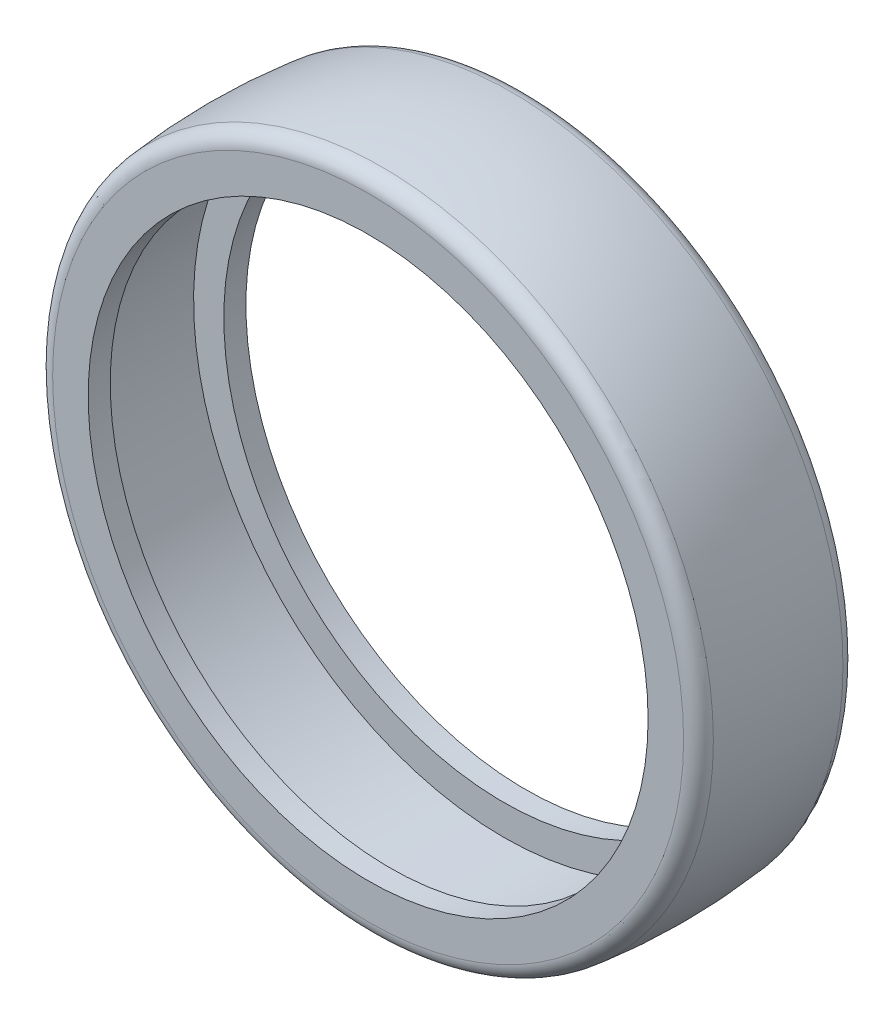
SolidWorks part; units mm, degrees
ref_plane "Front Plane" through (0, 0, 0) normal (0, 0, 1) x (1, 0, 0)
ref_plane "Top Plane" through (0, 0, 0) normal (0, 1, 0) x (1, 0, 0)
ref_plane "Right Plane" through (0, 0, 0) normal (1, 0, 0) x (0, 0, -1)
sketch "Sketch1" plane through (0, 0, 0) normal (1, 0, 0) x (0, 0, -1)
  line L0 (0, 0) -> (22.6821, 0) construction
  line L8 (-6, 26.625) -> (-3.9, 26.625)
  line L9 (-3.9, 26.625) -> (-3.9, 29.5)
  line L10 (-3.9, 29.5) -> (6.9, 29.5)
  line L11 (6.9, 29.5) -> (6.9, 26.625)
  line L12 (6.9, 26.625) -> (9, 26.625)
  line L13 (9, 26.625) -> (9, 31.83)
  line L14 (9, 31.83) -> (-6, 31.83)
  line L15 (-6, 31.83) -> (-6, 26.625)
  line L16 (-6, 26.625) -> (-3.9, 26.625)
  line L17 (-3.9, 26.625) -> (-3.9, 29.5)
  line L18 (-3.9, 29.5) -> (6.9, 29.5)
  line L19 (6.9, 29.5) -> (6.9, 26.625)
  line L20 (6.9, 26.625) -> (9, 26.625)
  line L21 (9, 26.625) -> (9, 31.83)
  line L22 (9, 31.83) -> (-6, 31.83)
  line L23 (-6, 31.83) -> (-6, 26.625)
  dimension "D1" = 0
revolve "Revolve1" add sketch "Sketch1" angle 360 about L0
sketch "Sketch2" plane through (0, 0, 0) normal (1, 0, 0) x (0, 0, -1)
  line L0 (-6, 31.83) -> (-6, -31.83) construction
  line L1 (9, -31.83) -> (9, 31.83) construction
  line L2 (9, -31.83) -> (9, 31.83) construction
  line L3 (9, 31.83) -> (-13.1922, 31.83) construction
  line L4 (-6, 31.33) -> (9, 31.33) construction
  line L5 (-6, 31.33) -> (-6, 34.2329)
  line L6 (-6, 34.2329) -> (9, 34.2329)
  line L7 (9, 34.2329) -> (9, 31.33)
  line L8 (0, 0) -> (21.0121, 0) construction
  arc A0 (-6, 31.33) -> (9, 31.33) centre (1.5, -24.67) cw
  dimension "D1" = 0.5
revolve "Cut-Revolve1" cut sketch "Sketch2" angle 360 about L8 region at (0, 32.9439, -1.5)
fillet "Fillet1" radius 1.5 2 edges at (31.33, 0, -9) (31.33, 0, 6)
sketch "Sketch3" plane through (0, 0, 0) normal (1, 0, 0) x (0, 0, -1)
  line L0 (6.9, 26.625) -> (6.9, -26.625) construction
  line L1 (6.9, 26.625) -> (6.9, -26.625) construction
  line L2 (6.9, 29.5) -> (6.9, -29.5) construction
  line L3 (6.9, 29.5) -> (6.9, -29.5) construction
  line L4 (-3.9, -29.5) -> (-3.9, 29.5) construction
  line L5 (-3.9, -29.5) -> (-3.9, 29.5) construction
  line L6 (0, 0) -> (25.8505, 0) construction
  line L7 (-3.9, 29.5) -> (6.9, 29.5)
  line L8 (-3.9, 29.5) -> (-3.9, 26.625)
  line L9 (-3.9, 26.625) -> (6.9, 26.625)
  line L10 (6.9, 29.5) -> (6.9, 26.625)
revolve "Revolve2" add sketch "Sketch3" angle 10 about L6 other way angle 10
